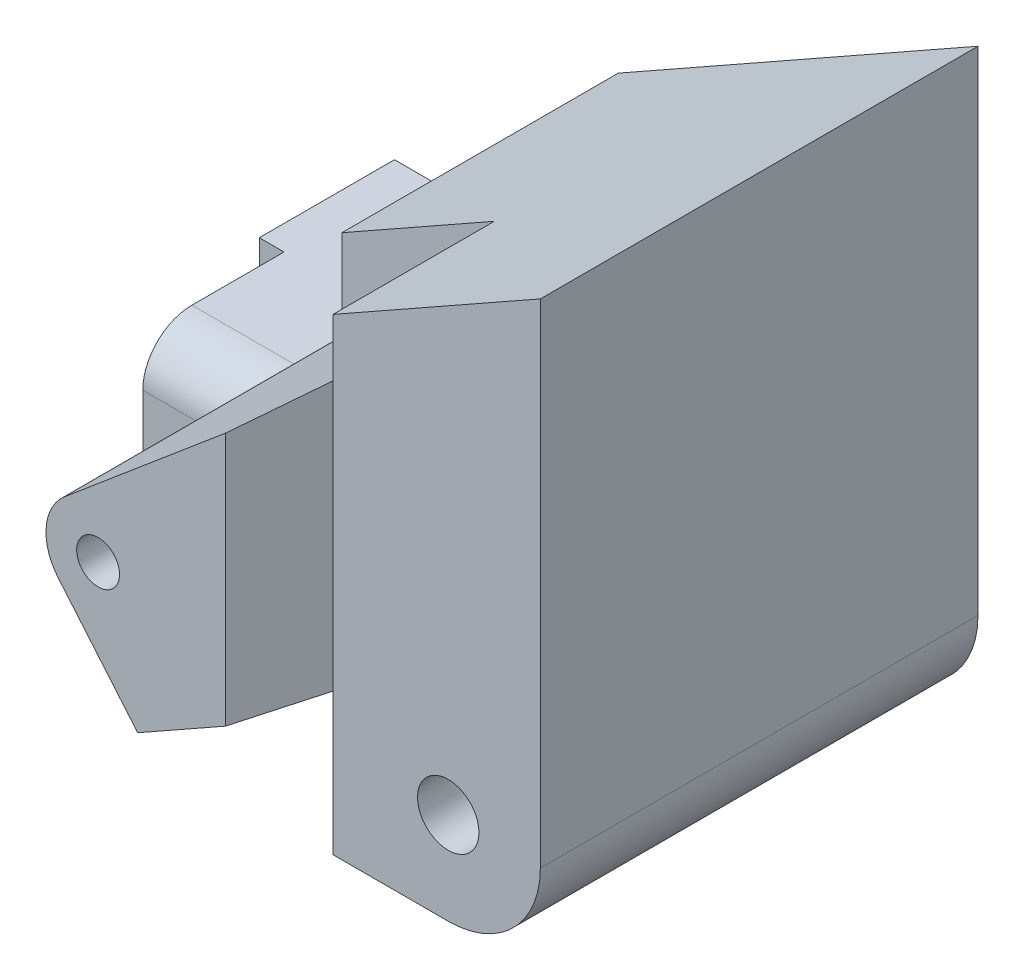
SolidWorks part; units mm, degrees
ref_plane "Front Plane" through (0, 0, 0) normal (0, 0, 1) x (1, 0, 0)
ref_plane "Top Plane" through (0, 0, 0) normal (0, 1, 0) x (1, 0, 0)
ref_plane "Right Plane" through (0, 0, 0) normal (1, 0, 0) x (0, 0, -1)
sketch "Sketch8" plane through (0, 0, 0) normal (0, 0, 1) x (1, 0, 0)
  line L0 (-16, -22.05) -> (16, -22.05)
  line L1 (22, -16.05) -> (22, 16.05)
  line L2 (22, 16.05) -> (-1.4244, 2.8208)
  line L3 (-1.4244, 2.8208) -> (-1.4244, -9.35)
  line L4 (-1.4244, -9.35) -> (-16, -9.35)
  line L5 (-16, -9.35) -> (-16, -22.05)
  line L6 (20.6357, -12.2407) -> (0.2561, 12.5601) construction
  line L7 (-22.35, 28.2019) -> (-9.65, 28.2019) construction
  line L8 (-22.35, 28.2019) -> (-22.35, -16.2481) construction
  line L9 (-22.35, -16.2481) -> (-9.65, -16.2481) construction
  line L10 (-9.65, 28.2019) -> (-9.65, -16.2481) construction
  line L15 (-22.35, -16.2481) -> (-9.65, -16.2481) construction
  line L16 (-22.35, -16.2481) -> (-22.35, -13.0681) construction
  line L17 (-22.35, -13.0681) -> (-9.65, -13.0681) construction
  line L18 (-9.65, -16.2481) -> (-9.65, -13.0681) construction
  line L19 (-22.35, 28.2019) -> (-9.65, 28.2019) construction
  line L20 (-22.35, 28.2019) -> (-22.35, 25.0219) construction
  line L21 (-22.35, 25.0219) -> (-9.65, 25.0219) construction
  line L22 (-9.65, 28.2019) -> (-9.65, 25.0219) construction
  line L23 (0.2561, 12.5601) -> (-9.443, -12.5325) construction
  line L24 (-9.443, -12.5325) -> (-1.716, -21.9358) construction
  line L25 (-1.716, -21.9358) -> (-12.9773, -31.1896) construction
  line L26 (-12.9773, -31.1896) -> (-4.9144, -41.0017) construction
  line L27 (-4.9144, -41.0017) -> (19.8093, -20.6857) construction
  line L28 (21.8727, -14.8204) -> (15.2944, 16.5983) construction
  line L29 (15.2944, 16.5983) -> (-4.9218, -1.1505) construction
  line L30 (-4.9218, -1.1505) -> (-2.4276, -13.063) construction
  line L31 (-2.4276, -13.063) -> (-16.6939, -16.05) construction
  line L32 (-16.6939, -16.05) -> (-14.0913, -28.4805) construction
  line L33 (-14.0913, -28.4805) -> (17.2296, -21.9227) construction
  line L34 (-22.35, -0.1424) -> (-22.35, 3.0376) construction
  line L35 (-22.35, -0.1424) -> (-9.65, -0.1424) construction
  line L36 (-9.65, -0.1424) -> (-9.65, 3.0376) construction
  line L37 (-22.35, 3.0376) -> (-9.65, 3.0376) construction
  line L38 (-22.35, 44.3076) -> (-22.35, 41.1276) construction
  line L39 (-22.35, 44.3076) -> (-9.65, 44.3076) construction
  line L40 (-9.65, 44.3076) -> (-9.65, 41.1276) construction
  line L41 (-22.35, 41.1276) -> (-9.65, 41.1276) construction
  line L42 (-22.35, 44.3076) -> (-22.35, -0.1424) construction
  line L43 (-9.65, 44.3076) -> (-9.65, -0.1424) construction
  line L44 (-16, 38.1217) -> (-16, 46.832) construction
  line L45 (-47.2944, 16.5983) -> (-27.0782, -1.1505) construction
  line L46 (-27.0782, -1.1505) -> (-29.5724, -13.063) construction
  line L47 (-53.8727, -14.8204) -> (-47.2944, 16.5983) construction
  line L48 (-17.9087, -28.4805) -> (-49.2296, -21.9227) construction
  line L49 (-15.3061, -16.05) -> (-17.9087, -28.4805) construction
  line L50 (-29.5724, -13.063) -> (-15.3061, -16.05) construction
  line L51 (-15.3644, -16.3284) -> (-16.9386, -15.9988)
  line L53 (-16, -9.35) -> (-14.3917, -9.35)
  line L55 (-16, -22.05) -> (-14.3917, -22.05)
  line L56 (-14.3917, -9.35) -> (-14.3917, -22.05)
  arc A0 (16, -22.05) -> (22, -16.05) centre (16, -16.05) ccw
  circle A1 centre (16, -16.05) radius 2
  circle A2 centre (-3.3, -9.7) radius 1.395
  arc A3 (19.8093, -20.6857) -> (20.6357, -12.2407) centre (16, -16.05) ccw construction
  circle A4 centre (-16, -25.7781) radius 6.1 construction
  arc A5 (17.2296, -21.9227) -> (21.8727, -14.8204) centre (16, -16.05) ccw construction
  circle A6 centre (-16, -9.6724) radius 6.1 construction
  arc A7 (-49.2296, -21.9227) -> (-53.8727, -14.8204) centre (-48, -16.05) cw construction
  point P11 (0, -22.05)
  point P13 (22, 0)
  point P22 (-9.65, 5.9769)
  point P25 (-16, -16.2481)
  point P32 (16, -16.05)
  point P33 (-16, 25.0219)
  point P46 (16, -16.05)
  dimension "D4" = 4
  dimension "D5" = 2.79
  dimension "D15" = 12.2
  dimension "D1" = 38
  dimension "D2" = 32
  dimension "D3" = 12.7
  dimension "D6" = 38.1
  dimension "D7" = 25
  dimension "D8" = 6.35
  dimension "D9" = 3.18
  dimension "D10" = 44.45
  dimension "D11" = 12.7
  dimension "D13" = 12.7
  dimension "D14" = 9.53
  dimension "D16" = 0.5
  dimension "D19" = 0.25
  dimension "D18" = 2
  dimension "D12" = 2
  dimension "D17" = 2
extrude "Boss-Extrude6" add sketch "Sketch8" along normal mid plane 18 contours A2 L4 L5 L0 A0 L1 L2 L3 A1 | L56 L4 L5 L0 region at (-15.1958, -15.7, 0) region at (7.4527, -7.5911, 0)
sketch "Sketch9" plane through (0, 0, 0) normal (0, 0, 1) x (1, 0, 0)
  line L0 (8.5, 4.6785) -> (-5.4872, -7.1034)
  line L1 (8.5, 4.6785) -> (8.5, -12.8207)
  line L2 (-0.7228, -18.0294) -> (8.5, -12.8207)
  line L3 (22, -16.05) -> (22, 16.05) construction
  line L4 (-5.8966, -11.8872) -> (-0.7228, -18.0294)
  line L5 (22, 16.05) -> (-1.4244, 2.8208) construction
  circle A0 centre (-3.3, -9.7) radius 1.395
  circle A1 centre (-3.3, -9.7) radius 1.395 construction
  arc A2 (-5.4872, -7.1034) -> (-5.8966, -11.8872) centre (-3.3, -9.7) ccw
  circle A3 centre (16, -16.05) radius 2 construction
  dimension "D1" = 6.5
  dimension "D3" = 2
  dimension "D2" = 13.5
extrude "Boss-Extrude7" add sketch "Sketch9" along normal blind 32 from surface starting at face at (2.1993, -9.0741, -9)
chamfer "Chamfer3" distance 3.5 angle 45 1 edges at (8.5, -4.0711, 23)
sketch "Sketch11" plane through (0, 0, 0) normal (0, 0, 1) x (1, 0, 0)
  line L10 (-16, -9.35) -> (-16, -22.05)
  line L11 (8.5, 4.6785) -> (8.5, -12.8207)
  line L12 (8.5, 8.4257) -> (8.5, -22.05)
  line L13 (8.5, -12.8207) -> (8.5, 4.6785) construction
  line L14 (8.5, -12.8207) -> (-0.7228, -18.0294)
  line L15 (-0.7228, -18.0294) -> (-5.8966, -11.8872)
  line L22 (-1.4244, 2.8208) -> (-1.4244, -3.6812)
  line L23 (-1.4244, -3.6812) -> (8.5, 4.6785)
  line L27 (-6.6769, -9.35) -> (-16, -9.35)
  line L29 (-16, -22.05) -> (16, -22.05)
  line L30 (22, -16.05) -> (22, 16.05)
  line L31 (22, 16.05) -> (-1.4244, 2.8208)
  line L39 (8.5, -22.05) -> (16, -22.05)
  line L40 (22, -16.05) -> (22, 16.05)
  line L41 (22, 16.05) -> (8.5, 8.4257)
  circle A2 centre (16, -16.05) radius 2
  circle A3 centre (16, -16.05) radius 2 construction
  arc A4 (-6.6769, -9.35) -> (-5.8966, -11.8872) centre (-3.3, -9.7) ccw
  arc A5 (16, -22.05) -> (22, -16.05) centre (16, -16.05) ccw
  arc A7 (16, -22.05) -> (22, -16.05) centre (16, -16.05) ccw
  dimension "D1" = 0
extrude "Boss-Extrude8" add sketch "Sketch11" along normal blind 28.5 from surface starting at face at (1.5568, -7.9879, -9)
extrude "Cut-Extrude1" cut sketch "Sketch8<4>" along normal through all from offset 0.2 contours L56 L4 L5 L0 region at (-15.1958, -15.7, 0) offset against normal yes
sketch "Sketch8<4>" plane through (0, 0, 0) normal (0, 0, 1) x (1, 0, 0) same geometry as "Sketch8"
fillet "Fillet5" radius 3.2 2 edges at (-10.5343, -9.35, 9) (-2.9458, -22.05, 9)
fillet "Fillet6" [suppressed] radius 3.2
sketch "Sketch1" plane through (0, 0, 0) normal (0, 0, 1) x (1, 0, 0)
  line L0 (19, 19.05) -> (19, -13.05)
  line L1 (-19, -19.05) -> (19, -19.05) construction
  line L2 (-19, -19.05) -> (-19, 19.05) construction
  line L3 (-19, 19.05) -> (19, 19.05) construction
  line L4 (19, -19.05) -> (19, 19.05) construction
  line L5 (-19, -19.05) -> (19, 19.05) construction
  line L6 (-19, 19.05) -> (19, -19.05) construction
  line L7 (-19, -19.05) -> (13, -19.05)
  line L8 (-19, -19.05) -> (-19, -9.6947) construction
  line L9 (9.7447, 19.05) -> (19, 19.05) construction
  line L10 (19, 19.05) -> (-19, -2.4109) construction
  line L11 (-19, -19.05) -> (-19, -2.4109) construction
  line L21 (19, 19.05) -> (-9.7362, 2.8209)
  line L22 (-19, -19.05) -> (-19, -13.05)
  line L24 (-25.35, 45.8289) -> (-12.65, 45.8289) construction
  line L25 (-25.35, 45.8289) -> (-25.35, 1.3789) construction
  line L26 (-25.35, 1.3789) -> (-12.65, 1.3789) construction
  line L27 (-12.65, 45.8289) -> (-12.65, 1.3789) construction
  line L28 (-25.35, 4.5589) -> (-12.65, 4.5589) construction
  line L29 (-25.35, 4.5589) -> (-25.35, 1.3789) construction
  line L30 (-25.35, 1.3789) -> (-12.65, 1.3789) construction
  line L31 (-12.65, 4.5589) -> (-12.65, 1.3789) construction
  line L32 (-12.65, 42.6489) -> (-25.35, 42.6489) construction
  line L33 (-12.65, 42.6489) -> (-12.65, 45.8289) construction
  line L34 (-12.65, 45.8289) -> (-25.35, 45.8289) construction
  line L35 (-25.35, 42.6489) -> (-25.35, 45.8289) construction
  circle A0 centre (13, -13.05) radius 2
  arc A1 (19, -13.05) -> (13, -19.05) centre (13, -13.05) cw
  arc A2 (9.7447, 19.05) -> (-19, -9.6947) centre (9.7447, -9.6947) ccw construction
  circle A6 centre (-6.3, -6.7) radius 1.397
  arc A8 (-9.7362, 2.8209) -> (-19, -13.05) centre (-0.7729, -13.05) ccw
  point P0 (0, 0)
  point P33 (-6.3, -6.7)
  point P39 (-19, 1.3789)
  dimension "D4" = 4
  dimension "D14" = 2.794
  dimension "D1" = 38
  dimension "D2" = 38.1
  dimension "D3" = 6
  dimension "D5" = 28.7447
  dimension "D6" = 25
  dimension "D12" = 12.7
  dimension "D13" = 6.35
  dimension "D16" = 32
  dimension "D17" = 12.7
  dimension "D18" = 44.45
  dimension "D19" = 3.18
extrude "Boss-Extrude1" [suppressed] add sketch "Sketch1" along normal blind 18
sketch "Sketch4" [suppressed] plane through (0, 0, 0) normal (0, 0, -1) x (-1, 0, 0)
  line L0 (-27.0252, 2.3358) -> (6.1642, -16.4082) construction
  line L2 (-5.5, 11.4257) -> (-5.5, -9.8207)
  line L3 (-19, 19.05) -> (9.7362, 2.8209) construction
  line L4 (-19, -13.05) -> (-19, 19.05) construction
  line L5 (-5.5, -9.8207) -> (2.1102, -14.1187)
  line L6 (6.7386, -12.8313) -> (9.2579, -8.3705)
  line L7 (8.8205, -4.4225) -> (-5.5, 11.4257)
  circle A0 centre (-13, -13.05) radius 2 construction
  arc A1 (8.8205, -4.4225) -> (9.2579, -8.3705) centre (6.3, -6.7) cw
  circle A2 centre (6.3, -6.7) radius 1.397 construction
  arc A3 (2.1102, -14.1187) -> (6.7386, -12.8313) centre (3.7807, -11.1608) ccw
  circle A4 centre (6.3, -6.7) radius 1.397
  point P23 (5.0681, -15.7892)
  dimension "D1" = 6.5
  dimension "D3" = 2
  dimension "D2" = 13.5
extrude "Boss-Extrude3" [suppressed] add sketch "Sketch4" along normal offset from surface (14 mm away) 32
sketch "Sketch2" [suppressed] plane through (0, 0, 0) normal (0, 0, -1) x (-1, 0, 0)
  line L0 (-19, -13.05) -> (-19, 19.05)
  line L2 (-19, 19.05) -> (9.7362, 2.8209) construction
  line L4 (-7.3412, -15.0445) -> (-5.5, -9.8207)
  line L5 (-19, 19.05) -> (-5.5, 11.4257)
  line L6 (-5.5, 11.4257) -> (-5.5, -9.8207)
  arc A0 (-19, -13.05) -> (-7.3412, -15.0445) centre (-13, -13.05) ccw
  arc A1 (-19, -13.05) -> (-13, -19.05) centre (-13, -13.05) ccw construction
  circle A2 centre (-13, -13.05) radius 2
  circle A3 centre (-13, -13.05) radius 2 construction
extrude "Boss-Extrude2" [suppressed] add sketch "Sketch2" along normal offset from surface (10.5 mm away) 28.5
fillet "Fillet1" [suppressed] radius 3.2
fillet "Fillet2" [suppressed] radius 2 tangent propagation no
chamfer "Chamfer1" [suppressed] distance 3.5 angle 45
sketch "Sketch6" [suppressed] plane through (0, 0, 18) normal (0, 0, 1) x (1, 0, 0)
  line L0 (25.2413, 1.3284) -> (-0.1036, -12.9854) construction
  line L2 (5.5, 11.4257) -> (5.5, -9.8207)
  line L3 (19, -13.05) -> (19, 19.05) construction
  line L4 (-8.8205, -4.4225) -> (5.5, 11.4257)
  line L5 (-9.2579, -8.3705) -> (-6.7386, -12.8313)
  line L6 (-2.1102, -14.1187) -> (5.5, -9.8207)
  line L7 (19, 19.05) -> (-9.7362, 2.8209) construction
  circle A0 centre (13, -13.05) radius 2 construction
  arc A1 (-8.8205, -4.4225) -> (-9.2579, -8.3705) centre (-6.3, -6.7) ccw
  circle A2 centre (-6.3, -6.7) radius 1.397 construction
  arc A3 (-6.7386, -12.8313) -> (-2.1102, -14.1187) centre (-3.7807, -11.1608) ccw
  circle A4 centre (-6.3, -6.7) radius 1.397
  point P19 (-5.0681, -15.7892)
  dimension "D1" = 6.5
  dimension "D3" = 2
  dimension "D2" = 13.5
extrude "Boss-Extrude4" [suppressed] add sketch "Sketch6" along normal offset from surface (14 mm away) 32
sketch "Sketch7" [suppressed] plane through (0, 0, 18) normal (0, 0, 1) x (1, 0, 0)
  line L0 (5.5, 11.4257) -> (5.5, -19.05)
  line L1 (-19, -19.05) -> (13, -19.05) construction
  line L2 (5.5, 11.4257) -> (-9.7362, 2.8209) construction
  line L29 (5.5, 11.4257) -> (19, 19.05)
  line L30 (19, 19.05) -> (19, -13.05)
  line L31 (5.5, -19.05) -> (13, -19.05)
  circle A0 centre (13, -13.05) radius 2
  circle A1 centre (13, -13.05) radius 2 construction
  arc A9 (19, -13.05) -> (13, -19.05) centre (13, -13.05) cw
  arc A10 (13, -19.05) -> (19, -13.05) centre (13, -13.05) ccw construction
extrude "Boss-Extrude5" [suppressed] add sketch "Sketch7" along normal offset from surface (10.5 mm away) 28.5
fillet "Fillet4" [suppressed] radius 3.2 tangent propagation no
chamfer "Chamfer2" [suppressed] distance 3.5 angle 45
fillet "Fillet3" [suppressed] radius 2 tangent propagation no
